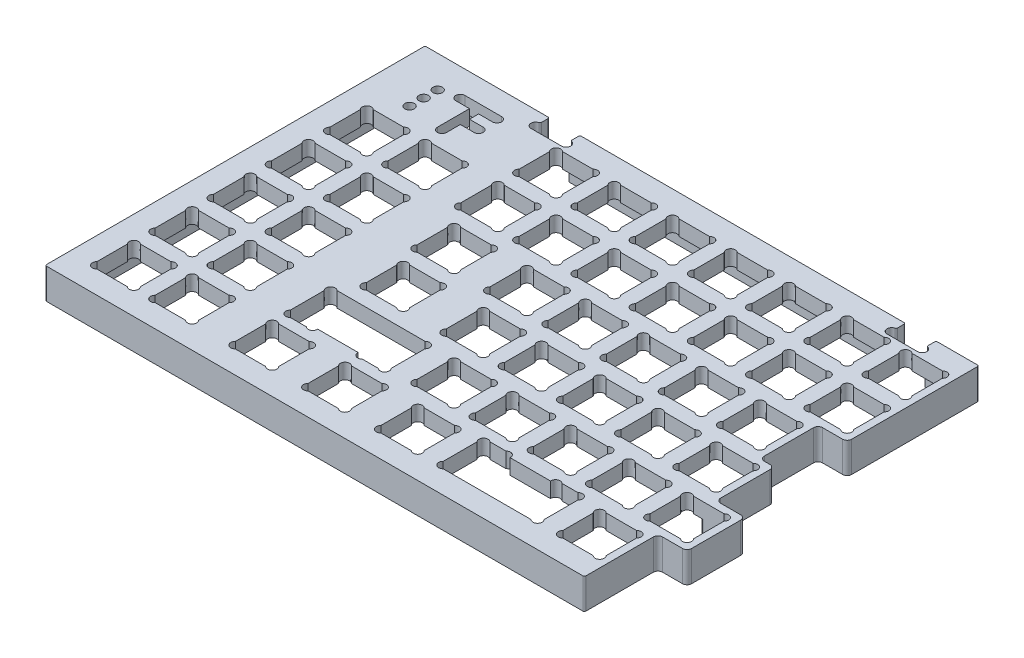
SolidWorks part; units mm, degrees
material "6061-T6 (SS)"
ref_plane "Front Plane" through (0, 0, 0) normal (0, 0, 1) x (1, 0, 0)
ref_plane "Top Plane" through (0, 0, 0) normal (0, 1, 0) x (1, 0, 0)
ref_plane "Right Plane" through (0, 0, 0) normal (1, 0, 0) x (0, 0, -1)
sketch "Sketch1" plane through (0, 0, 0) normal (0, 1, 0) x (1, 0, 0)
  line L0 (0, 0) -> (0, 124.3)
  line L1 (0, 124.3) -> (181.2125, 124.3)
  line L2 (181.2125, 124.3) -> (181.2125, 81.2)
  line L3 (181.2125, 81.2) -> (171.6875, 81.2)
  line L4 (171.6875, 81.2) -> (171.6875, 62.15)
  line L5 (171.6875, 62.15) -> (176.45, 62.15)
  line L6 (176.45, 62.15) -> (176.45, 43.1)
  line L7 (176.45, 43.1) -> (185.975, 43.1)
  line L8 (185.975, 43.1) -> (185.975, 24.05)
  line L9 (185.975, 24.05) -> (176.45, 24.05)
  line L10 (176.45, 24.05) -> (176.45, 0)
  line L11 (176.45, 0) -> (0, 0)
  dimension "D2" = 181.2125
  dimension "D3" = 43.1
  dimension "D4" = 4.7625
  dimension "D5" = 9.525
  dimension "D6" = 19.05
  dimension "D1" = 24.05
extrude "Plate Frame" add sketch "Sketch1" along normal blind 5
sketch "Sketch4" plane through (0, 5, 0) normal (0, 1, 0) x (1, 0, 0)
  line L0 (14.525, 90.725) -> (33.575, 90.725) construction
  line L1 (33.575, 90.725) -> (33.575, 71.675) construction
  line L2 (33.575, 71.675) -> (33.575, 52.625) construction
  line L3 (33.575, 52.625) -> (33.575, 33.575) construction
  line L4 (33.575, 33.575) -> (33.575, 14.525) construction
  line L5 (33.575, 14.525) -> (14.525, 14.525) construction
  line L6 (14.525, 14.525) -> (14.525, 33.575) construction
  line L7 (14.525, 33.575) -> (14.525, 52.625) construction
  line L8 (14.525, 52.625) -> (14.525, 71.675) construction
  line L9 (14.525, 71.675) -> (14.525, 90.725) construction
  line L10 (14.525, 71.675) -> (33.575, 71.675) construction
  line L11 (14.525, 52.625) -> (33.575, 52.625) construction
  line L12 (14.525, 33.575) -> (33.575, 33.575) construction
  line L13 (57.3875, 109.775) -> (57.3875, 90.725) construction
  line L14 (57.3875, 90.725) -> (76.4375, 90.725) construction
  line L15 (76.4375, 90.725) -> (76.4375, 109.775) construction
  line L16 (76.4375, 109.775) -> (95.4875, 109.775) construction
  line L17 (95.4875, 109.775) -> (114.5375, 109.775) construction
  line L18 (114.5375, 109.775) -> (133.5875, 109.775) construction
  line L19 (133.5875, 109.775) -> (152.6375, 109.775) construction
  line L20 (152.6375, 109.775) -> (171.6875, 109.775) construction
  line L21 (171.6875, 109.775) -> (171.6875, 90.725) construction
  line L22 (171.6875, 90.725) -> (152.6375, 90.725) construction
  line L23 (152.6375, 90.725) -> (133.5875, 90.725) construction
  line L24 (133.5875, 90.725) -> (114.5375, 90.725) construction
  line L25 (114.5375, 90.725) -> (95.4875, 90.725) construction
  line L26 (95.4875, 90.725) -> (76.4375, 90.725) construction
  line L27 (57.3875, 109.775) -> (76.4375, 109.775) construction
  line L28 (95.4875, 109.775) -> (95.4875, 90.725) construction
  line L29 (114.5375, 90.725) -> (114.5375, 109.775) construction
  line L30 (133.5875, 109.775) -> (133.5875, 90.725) construction
  line L31 (152.6375, 90.725) -> (152.6375, 109.775) construction
  line L32 (62.15, 71.675) -> (85.9625, 71.675) construction
  line L33 (85.9625, 71.675) -> (105.0125, 71.675) construction
  line L34 (105.0125, 71.675) -> (124.0625, 71.675) construction
  line L35 (124.0625, 71.675) -> (143.1125, 71.675) construction
  line L36 (143.1125, 71.675) -> (162.1625, 71.675) construction
  line L37 (90.725, 52.625) -> (109.775, 52.625) construction
  line L38 (109.775, 52.625) -> (128.825, 52.625) construction
  line L39 (128.825, 52.625) -> (147.875, 52.625) construction
  line L40 (147.875, 52.625) -> (166.925, 52.625) construction
  line L41 (100.25, 33.575) -> (119.3, 33.575) construction
  line L42 (119.3, 33.575) -> (138.35, 33.575) construction
  line L43 (138.35, 33.575) -> (157.4, 33.575) construction
  line L44 (157.4, 33.575) -> (176.45, 33.575) construction
  line L45 (171.6875, 71.675) -> (162.1625, 71.675) construction
  line L46 (171.6875, 62.15) -> (171.6875, 81.2) construction
  line L49 (59.7687, 14.525) -> (83.5812, 14.525) construction
  line L50 (83.5812, 14.525) -> (107.3937, 14.525) construction
  line L51 (64.5312, 52.625) -> (90.725, 52.625) construction
  line L52 (107.3937, 14.525) -> (166.925, 14.525) construction
  point P0 (14.525, 14.525)
  point P1 (33.575, 14.525)
  point P2 (33.575, 33.575)
  point P3 (14.525, 33.575)
  point P4 (14.525, 52.625)
  point P5 (33.575, 52.625)
  point P6 (33.575, 71.675)
  point P7 (14.525, 71.675)
  point P8 (14.525, 90.725)
  point P9 (33.575, 90.725)
  point P12 (57.3875, 109.775)
  point P21 (57.3875, 90.725)
  point P22 (76.4375, 90.725)
  point P23 (76.4375, 109.775)
  point P24 (95.4875, 109.775)
  point P25 (95.4875, 90.725)
  point P26 (114.5375, 90.725)
  point P27 (114.5375, 109.775)
  point P28 (133.5875, 109.775)
  point P29 (133.5875, 90.725)
  point P30 (152.6375, 90.725)
  point P31 (152.6375, 109.775)
  point P32 (171.6875, 109.775)
  point P33 (171.6875, 90.725)
  point P44 (85.9625, 71.675)
  point P49 (62.15, 71.675)
  point P50 (105.0125, 71.675)
  point P51 (124.0625, 71.675)
  point P52 (143.1125, 71.675)
  point P53 (162.1625, 71.675)
  point P54 (90.725, 52.625)
  point P55 (109.775, 52.625)
  point P56 (128.825, 52.625)
  point P57 (147.875, 52.625)
  point P58 (166.925, 52.625)
  point P59 (100.25, 33.575)
  point P60 (119.3, 33.575)
  point P61 (138.35, 33.575)
  point P62 (157.4, 33.575)
  point P63 (176.45, 33.575)
  point P81 (83.5812, 14.525)
  point P82 (107.3937, 14.525)
  point P83 (64.5312, 52.625)
  point P90 (166.925, 14.525)
  point P94 (59.7687, 14.525)
  dimension "D1" = 19.05
  dimension "D2" = 9.525
  dimension "D3" = 23.8125
  dimension "D4" = 23.8125
  dimension "D6" = 9.525
  dimension "D5" = 4.7625
  dimension "D7" = 9.525
  dimension "D8" = 23.8125
  dimension "D9" = 26.1938
  dimension "D10" = 26.1938
  dimension "D11" = 59.5312
sketch "Sketch2" plane through (0, 5, 0) normal (0, 1, 0) x (1, 0, 0)
  line L4 (7.425, 19.5037) -> (7.425, 9.5463)
  line L5 (7.425, 21.625) -> (21.625, 21.625) construction
  line L6 (7.425, 21.625) -> (7.425, 7.425) construction
  line L7 (7.425, 7.425) -> (21.625, 7.425) construction
  line L8 (21.625, 21.625) -> (21.625, 7.425) construction
  line L9 (7.425, 21.625) -> (21.625, 7.425) construction
  line L10 (7.425, 7.425) -> (21.625, 21.625) construction
  line L11 (9.5463, 7.425) -> (19.5037, 7.425)
  line L12 (21.625, 19.5037) -> (21.625, 9.5463)
  line L13 (9.5463, 21.625) -> (19.5037, 21.625)
  arc A8 (7.425, 19.5037) -> (9.5463, 21.625) centre (8.4857, 20.5643) cw
  arc A9 (21.625, 19.5037) -> (19.5037, 21.625) centre (20.5643, 20.5643) ccw
  arc A10 (21.625, 9.5463) -> (19.5037, 7.425) centre (20.5643, 8.4857) cw
  arc A11 (9.5463, 7.425) -> (7.425, 9.5463) centre (8.4857, 8.4857) cw
  point P0 (14.525, 14.525)
  dimension "D2" = 1.5
  dimension "D1" = 14.2
extrude "1U" cut sketch "Sketch2" against normal through all
pattern_sketch "Sketch-Pattern1" of "1U" driven by "Sketch4"
sketch "Sketch5" plane through (0, 5, 0) normal (0, 1, 0) x (1, 0, 0)
  line L0 (107.3937, 14.525) -> (166.925, 14.525) construction
  line L1 (69.2937, 33.575) -> (100.25, 33.575) construction
  point P0 (69.2937, 33.575)
  point P1 (137.1594, 14.525)
  point P4 (137.1594, 14.525)
  dimension "D1" = 30.9563
sketch "Sketch14" plane through (0, 5, 0) normal (0, 1, 0) x (1, 0, 0)
  line L9 (52.7937, 40.625) -> (60.4437, 32.975) construction
  line L10 (52.7937, 25.325) -> (62.2437, 25.325) construction
  line L11 (62.2437, 26.525) -> (76.3437, 26.525) construction
  line L12 (76.3437, 25.325) -> (85.7937, 25.325) construction
  line L13 (52.7937, 25.325) -> (60.4437, 32.975) construction
  line L14 (52.7937, 40.625) -> (85.7937, 40.625) construction
  line L15 (85.7937, 40.625) -> (85.7937, 25.325) construction
  line L16 (85.7937, 40.625) -> (78.1437, 32.975) construction
  line L17 (52.7937, 25.325) -> (52.7937, 40.625) construction
  line L18 (62.2437, 26.525) -> (62.2437, 25.325) construction
  line L19 (76.3437, 26.525) -> (76.3437, 25.325) construction
  line L20 (76.3437, 26.525) -> (62.2437, 40.625) construction
  line L21 (78.1437, 32.975) -> (85.7937, 25.325) construction
  line L22 (76.3437, 25.325) -> (81.0687, 30.05) construction
  line L23 (62.2437, 25.325) -> (57.5187, 30.05) construction
  line L24 (54.9151, 40.625) -> (83.6724, 40.625)
  line L25 (85.7937, 38.5037) -> (85.7937, 27.4463)
  line L26 (83.6724, 25.325) -> (78.4651, 25.325)
  line L27 (75.9109, 26.525) -> (62.6766, 26.525)
  line L28 (60.1224, 25.325) -> (54.9151, 25.325)
  line L29 (52.7937, 27.4463) -> (52.7937, 38.5037)
  arc A6 (52.7937, 38.5037) -> (54.9151, 40.625) centre (53.8544, 39.5643) cw
  arc A7 (85.7937, 38.5037) -> (83.6724, 40.625) centre (84.7331, 39.5643) ccw
  arc A8 (85.7937, 27.4463) -> (83.6724, 25.325) centre (84.7331, 26.3857) cw
  arc A9 (78.4651, 25.325) -> (75.9109, 26.525) centre (77.4044, 26.3857) cw
  arc A10 (60.1224, 25.325) -> (62.6766, 26.525) centre (61.1831, 26.3857) ccw
  arc A11 (54.9151, 25.325) -> (52.7937, 27.4463) centre (53.8544, 26.3857) cw
  point P38 (69.2937, 33.575)
  dimension "D1" = 45
  dimension "D3" = 1.5
  dimension "D2" = 45
  dimension "D6" = 15.3
  dimension "D7" = 14.1
  dimension "D8" = 33
  dimension "D9" = 14.1
extrude "LeftShift" cut sketch "Sketch14" against normal up to next
sketch "Sketch7" plane through (0, 5, 0) normal (0, 1, 0) x (1, 0, 0)
  line L9 (120.6594, 22.775) -> (130.1094, 22.775) construction
  line L19 (130.1094, 22.775) -> (130.1094, 21.575) construction
  line L20 (130.1094, 21.575) -> (144.2094, 21.575) construction
  line L21 (144.2094, 21.575) -> (144.2094, 22.775) construction
  line L22 (144.2094, 22.775) -> (153.6594, 22.775) construction
  line L23 (153.6594, 22.775) -> (153.6594, 7.475) construction
  line L24 (153.6594, 7.475) -> (120.6594, 7.475) construction
  line L25 (120.6594, 7.475) -> (120.6594, 22.775) construction
  line L26 (130.1094, 21.575) -> (144.2094, 7.475) construction
  line L27 (120.6594, 7.475) -> (128.3094, 15.125) construction
  line L28 (128.3094, 15.125) -> (120.6594, 22.775) construction
  line L29 (153.6594, 7.475) -> (146.0094, 15.125) construction
  line L30 (146.0094, 15.125) -> (153.6594, 22.775) construction
  line L31 (144.2094, 22.775) -> (148.9344, 18.05) construction
  line L32 (130.1094, 22.775) -> (125.3844, 18.05) construction
  line L33 (120.6594, 20.6537) -> (120.6594, 9.5963)
  line L34 (122.7807, 7.475) -> (151.5381, 7.475)
  line L35 (153.6594, 9.5963) -> (153.6594, 20.6537)
  line L36 (151.5381, 22.775) -> (146.3307, 22.775)
  line L37 (143.7765, 21.575) -> (130.5422, 21.575)
  line L38 (127.9881, 22.775) -> (122.7807, 22.775)
  arc A13 (120.6594, 20.6537) -> (122.7807, 22.775) centre (121.72, 21.7143) cw
  arc A14 (127.9881, 22.775) -> (130.5422, 21.575) centre (129.0487, 21.7143) cw
  arc A15 (146.3307, 22.775) -> (143.7765, 21.575) centre (145.27, 21.7143) ccw
  arc A16 (151.5381, 22.775) -> (153.6594, 20.6537) centre (152.5987, 21.7143) cw
  arc A17 (153.6594, 9.5963) -> (151.5381, 7.475) centre (152.5987, 8.5357) cw
  arc A18 (122.7807, 7.475) -> (120.6594, 9.5963) centre (121.72, 8.5357) cw
  point P10 (137.1594, 14.525)
  dimension "D13" = 1.5
  dimension "D2" = 33
  dimension "D3" = 14.1
  dimension "D4" = 14.1
  dimension "D5" = 15.3
  dimension "D11" = 45
  dimension "D12" = 45
extrude "LeftSpace" cut sketch "Sketch7" against normal through all
sketch "Sketch8" plane through (0, 0, 0) normal (0, -1, 0) x (1, 0, 0)
  line L0 (176.45, 0) -> (0, 0)
  line L1 (0, 0) -> (0, -124.3)
  line L2 (0, -124.3) -> (181.2125, -124.3)
  line L3 (181.2125, -124.3) -> (181.2125, -81.2)
  line L4 (181.2125, -81.2) -> (171.6875, -81.2)
  line L5 (171.6875, -81.2) -> (171.6875, -62.15)
  line L6 (171.6875, -62.15) -> (176.45, -62.15)
  line L7 (176.45, -62.15) -> (176.45, -43.1)
  line L8 (176.45, -43.1) -> (185.975, -43.1)
  line L9 (185.975, -43.1) -> (185.975, -24.05)
  line L10 (185.975, -24.05) -> (176.45, -24.05)
  line L11 (176.45, -24.05) -> (176.45, 0)
  line L12 (5, -5) -> (174.025, -5)
  line L13 (174.025, -5) -> (174.025, -26.475)
  line L15 (174.025, -26.475) -> (183.55, -26.475)
  line L16 (183.55, -26.475) -> (183.55, -40.675)
  line L17 (183.55, -40.675) -> (174.025, -40.675)
  line L19 (174.025, -40.675) -> (174.025, -59.725)
  line L20 (174.025, -59.725) -> (169.2625, -59.725)
  line L22 (169.2625, -59.725) -> (169.2625, -83.625)
  line L24 (169.2625, -83.625) -> (178.7875, -83.625)
  line L25 (178.7875, -83.625) -> (178.7875, -119.3)
  line L26 (178.7875, -119.3) -> (5, -119.3)
  line L27 (5, -119.3) -> (5, -5)
  line L41 (174.025, -9.5463) -> (174.025, -19.5037) construction
  line L42 (171.4713, -26.475) -> (181.4287, -26.475) construction
  line L43 (183.55, -28.5963) -> (183.55, -38.5537) construction
  line L44 (181.4287, -40.675) -> (171.4713, -40.675) construction
  line L45 (174.025, -47.6463) -> (174.025, -57.6037) construction
  line L46 (171.9037, -59.725) -> (161.9463, -59.725) construction
  line L47 (169.2625, -66.6963) -> (169.2625, -76.6537) construction
  line L48 (166.7088, -83.625) -> (176.6662, -83.625) construction
  line L49 (178.7875, -85.7463) -> (178.7875, -95.7037) construction
  dimension "D1" = 5
  dimension "D2" = 5
  dimension "D3" = 5
extrude "Lip" add sketch "Sketch8" along normal blind 5
sketch "Sketch17" plane through (0, 5, 0) normal (0, 1, 0) x (1, 0, 0)
  line L0 (40.6875, 124.3) -> (50.6875, 124.3) construction
  line L1 (50.6875, 124.3) -> (50.6875, 118.275) construction
  line L2 (50.6875, 118.275) -> (40.6875, 118.275) construction
  line L3 (40.6875, 118.275) -> (40.6875, 124.3) construction
  line L4 (40.6875, 121.275) -> (40.6875, 124.3)
  line L5 (40.6875, 124.3) -> (50.6875, 124.3)
  line L6 (50.6875, 124.3) -> (50.6875, 121.275)
  line L7 (50.6875, 118.275) -> (40.6875, 118.275)
  line L8 (157.1875, 124.3) -> (167.1875, 124.3) construction
  line L9 (167.1875, 124.3) -> (167.1875, 118.275) construction
  line L10 (167.1875, 118.275) -> (157.1875, 118.275) construction
  line L11 (157.1875, 118.275) -> (157.1875, 124.3) construction
  line L12 (157.1875, 121.275) -> (157.1875, 124.3)
  line L13 (157.1875, 124.3) -> (167.1875, 124.3)
  line L14 (167.1875, 124.3) -> (167.1875, 121.275)
  line L15 (167.1875, 118.275) -> (157.1875, 118.275)
  line L16 (181.2125, 124.3) -> (0, 124.3) construction
  line L17 (57.3875, 109.775) -> (76.4375, 109.775) construction
  line L18 (171.6875, 109.775) -> (171.6875, 90.725) construction
  line L19 (45.6875, 124.3) -> (45.6875, 118.275) construction
  line L20 (162.1875, 118.275) -> (162.1875, 124.3) construction
  arc A0 (40.6875, 118.275) -> (40.6875, 121.275) centre (40.6875, 119.775) cw
  arc A1 (50.6875, 118.275) -> (50.6875, 121.275) centre (50.6875, 119.775) ccw
  arc A2 (157.1875, 118.275) -> (157.1875, 121.275) centre (157.1875, 119.775) cw
  arc A3 (167.1875, 118.275) -> (167.1875, 121.275) centre (167.1875, 119.775) ccw
  dimension "D1" = 1.5
  dimension "D2" = 1.5
  dimension "D3" = 10
  dimension "D4" = 8.5
  dimension "D5" = 9.5
  dimension "D6" = 116.5
extrude "USB-Slots" cut sketch "Sketch17" against normal through all
sketch "Sketch12" plane through (0, 5, 0) normal (0, 1, 0) x (1, 0, 0)
  line L0 (14.525, 90.725) -> (33.575, 90.725) construction
  circle A0 centre (14.525, 113.925) radius 1.55
  circle A1 centre (14.525, 109.325) radius 1.55
  circle A2 centre (14.525, 104.725) radius 1.55
  dimension "D1" = 3.1
  dimension "D2" = 4.6
  dimension "D3" = 4.6
  dimension "D4" = 14
extrude "LockLeds" cut sketch "Sketch12" against normal through all
sketch "Sketch15" plane through (0, 5, 0) normal (0, 1, 0) x (1, 0, 0)
  line L0 (20.525, 115.325) -> (32.525, 115.325) construction
  line L1 (20.525, 116.825) -> (32.525, 116.825)
  line L2 (20.525, 113.825) -> (32.525, 113.825)
  line L3 (26.525, 115.325) -> (26.525, 103.325) construction
  line L4 (28.025, 115.325) -> (28.025, 103.325)
  line L5 (25.025, 115.325) -> (25.025, 103.325)
  line L6 (26.525, 109.325) -> (32.525, 109.325) construction
  line L7 (26.525, 110.825) -> (32.525, 110.825)
  line L8 (26.525, 107.825) -> (32.525, 107.825)
  line L9 (26.525, 109.325) -> (14.525, 109.325) construction
  arc A0 (20.525, 116.825) -> (20.525, 113.825) centre (20.525, 115.325) ccw
  arc A1 (32.525, 113.825) -> (32.525, 116.825) centre (32.525, 115.325) ccw
  arc A2 (28.025, 115.325) -> (25.025, 115.325) centre (26.525, 115.325) ccw
  arc A3 (25.025, 103.325) -> (28.025, 103.325) centre (26.525, 103.325) ccw
  arc A4 (26.525, 110.825) -> (26.525, 107.825) centre (26.525, 109.325) ccw
  arc A5 (32.525, 107.825) -> (32.525, 110.825) centre (32.525, 109.325) ccw
  point P2 (26.525, 115.325)
  point P7 (26.525, 109.325)
  point P14 (29.525, 109.325)
  dimension "D2" = 1.5
  dimension "D3" = 1.5
  dimension "D4" = 1.5
  dimension "D1" = 12
  dimension "D5" = 12
extrude "Logo" cut sketch "Sketch15" against normal through all contours L2 A1 L1 A0 | L5 A3 L4 A2 | L8 A5 L7 A4
sketch "Sketch16" plane through (0, 0, 0) normal (0, 1, 0) x (1, 0, 0)
  circle A0 centre (177.7268, 115.8143) radius 1.5
  circle A1 centre (177.7268, 103.7357) radius 1.5
  circle A2 centre (177.7268, 96.7643) radius 1.5
  circle A3 centre (177.7268, 84.6857) radius 1.5
  circle A4 centre (168.2018, 77.7143) radius 1.5
  circle A5 centre (168.2018, 65.6357) radius 1.5
  circle A6 centre (172.9643, 58.6643) radius 1.5
  circle A7 centre (172.9643, 46.5857) radius 1.5
  circle A8 centre (182.4893, 39.6143) radius 1.5
  circle A9 centre (182.4893, 27.5357) radius 1.5
  circle A10 centre (172.9643, 20.5643) radius 1.5
  circle A11 centre (172.9643, 8.4857) radius 1.5
  arc A14 (178.7875, 114.7537) -> (176.6662, 116.875) centre (177.7268, 115.8143) ccw construction
extrude "Cut-Extrude10" cut sketch "Sketch16" against normal through all
sketch "Sketch22" plane through (0, -5, 0) normal (0, -1, 0) x (1, 0, 0)
  line L0 (0, -62.15) -> (5, -62.15) construction
  line L1 (0, 0) -> (0, -124.3) construction
  line L2 (5, -5) -> (5, -119.3) construction
  line L3 (88.225, 0) -> (88.225, -5) construction
  line L4 (176.45, 0) -> (0, 0) construction
  line L5 (174.025, -5) -> (5, -5) construction
  line L6 (103.7125, -124.3) -> (103.7125, -119.3) construction
  line L8 (52.1103, -119.3) -> (155.7647, -119.3) construction
  line L9 (178.7125, -121.8) -> (103.7125, -121.8) construction
  line L10 (103.7125, -121.8) -> (2.5, -121.8) construction
  line L11 (2.5, -121.8) -> (2.5, -62.15) construction
  line L12 (2.5, -62.15) -> (2.5, -2.5) construction
  line L13 (2.5, -2.5) -> (88.225, -2.5) construction
  line L14 (88.225, -2.5) -> (173.95, -2.5) construction
  line L15 (176.45, -24.05) -> (176.45, 0) construction
  line L16 (181.2125, -124.3) -> (181.2125, -81.2) construction
  line L17 (50.6875, -124.3) -> (157.1875, -124.3) construction
  point P14 (0, 0)
  point P16 (0, 0)
  point P18 (178.7125, -121.8)
  point P19 (103.7125, -121.8)
  point P20 (2.5, -121.8)
  point P21 (2.5, -62.15)
  point P22 (2.5, -2.5)
  point P23 (88.225, -2.5)
  point P24 (173.95, -2.5)
  point P31 (0, 0)
  point P33 (1.2373, -57.9371)
  point P34 (1.5286, -65.0112)
  point P35 (2.5, -62.15)
  point P36 (115.4795, -122.0296)
  point P37 (103.7125, -121.8)
  point P38 (88.225, -2.5)
  point P39 (0, 0)
  point P40 (88.225, -2.5)
  point P45 (110.3704, -121.8)
  point P46 (103.9375, -121.8)
  point P47 (0, 0)
  dimension "D1" = 2.5
  dimension "D2" = 2.5
  dimension "D3" = 75
hole_wizard "M2x0.4 Tapped Hole1" positions "Sketch19" profile "Sketch20" tap size "M2x0.4" standard "ANSI Metric"
sketch "Sketch19" plane through (0, -5, 0) normal (0, -1, 0) x (-1, 0, 0)
  point P2 (-178.7125, 121.8)
  point P5 (-103.7125, 121.8)
  point P8 (-2.5, 121.8)
  point P11 (-2.5, 62.15)
  point P14 (-2.5, 2.5)
  point P17 (-88.225, 2.5)
  point P20 (-173.95, 2.5)
sketch "Sketch20" plane through (178.7125, -5, -121.8) normal (1, 0, 0) x (0, 0, -1)
  line L0 (0, 0) -> (0, 5.6807)
  line L1 (0, 5.6807) -> (0.8, 5.2)
  line L2 (0.8, 5.2) -> (0.8, 0.225)
  line L3 (0.8, 0.225) -> (1.025, 0)
  line L5 (1.025, 0) -> (0, 0)
  line L6 (-0.8, 0.225) -> (-1.025, 0) construction
  line L10 (0, 5.6807) -> (-0.8, 5.2) construction
  line L11 (0, -6.35) -> (0, 107.95) construction
  dimension "Tap Drill Dia." = 1.6
  dimension "Tap Drill Depth" = 5.2
  dimension "Near C'Sink Dia." = 2.05
  dimension "Near C'Sink Angle" = 90
  dimension "Drill Angle" = 118
cosmetic thread "Hole Thread1" parameters "D1"=4, "D2"=2
cosmetic thread "Hole Thread2" parameters "D1"=4, "D2"=2
cosmetic thread "Hole Thread3" parameters "D1"=4, "D2"=2
cosmetic thread "Hole Thread4" parameters "D1"=4, "D2"=2
cosmetic thread "Hole Thread5" parameters "D1"=4, "D2"=2
cosmetic thread "Hole Thread6" parameters "D1"=4, "D2"=2
cosmetic thread "Hole Thread7" parameters "D1"=4, "D2"=2
fillet "Fillet1" radius 1.5 12 edges at (171.6875, 0, -62.15) (176.45, 0, -43.1) (176.45, 0, -62.15) (181.2125, 0, -81.2) (171.6875, 0, -81.2) (185.975, 0, -43.1) (185.975, 0, -24.05) (176.45, 0, -24.05) (174.025, -2.5, -5) (5, -2.5, -5) (5, -2.5, -119.3) (178.7875, -2.5, -119.3)
fillet "Fillet2" radius 0.5 16 edges at (169.2625, -2.5, -83.625) (169.2625, -2.5, -59.725) (174.025, -2.5, -40.675) (174.025, -2.5, -26.475) (40.6875, 0, -124.3) (50.6875, 0, -124.3) (50.6875, 0, -121.275) (40.6875, 0, -121.275) (157.1875, 0, -124.3) (167.1875, 0, -124.3) (167.1875, 0, -121.275) (157.1875, 0, -121.275) (0, 0, 0) (0, 0, -124.3) (181.2125, 0, -124.3) (176.45, 0, 0)
equation "\"D2@Sketch4\"=19.05/2"
equation "\"D3@Sketch4\"=19.05/2 + (19.05*1.5)/2"
equation "\"D4@Sketch4\"=19.05/2 + 19.05*.25 + 19.05/2"
equation "\"D6@Sketch4\"=19.05/2"
equation "\"D5@Sketch4\"=19.05/4"
equation "\"D7@Sketch4\"=19.05/2"
equation "\"D5@Sketch1\"=19.05/2"
equation "\"D4@Sketch1\"=19.05/4"
equation "\"D8@Sketch4\"=19.05*1.25"
equation "\"D9@Sketch4\"=19.05/2 + 19.05*1.75/2"
equation "\"D10@Sketch4\"=19.05/2 + 19.05*.25 + 19.05*1.25/2"
equation "\"D11@Sketch4\"=19.05*1.25/2 + 19.05*2 + 19.05/2"
equation "\"D1@Sketch5\"=19.05*2.25/2 + 19.05/2"
equation "\"D3@Sketch1\"=19.05*2 + 5"
equation "\"D1@Sketch1\"=19.05 + 5"
equation "\"D2@Sketch1\"=9.25*19.05 + 5"
